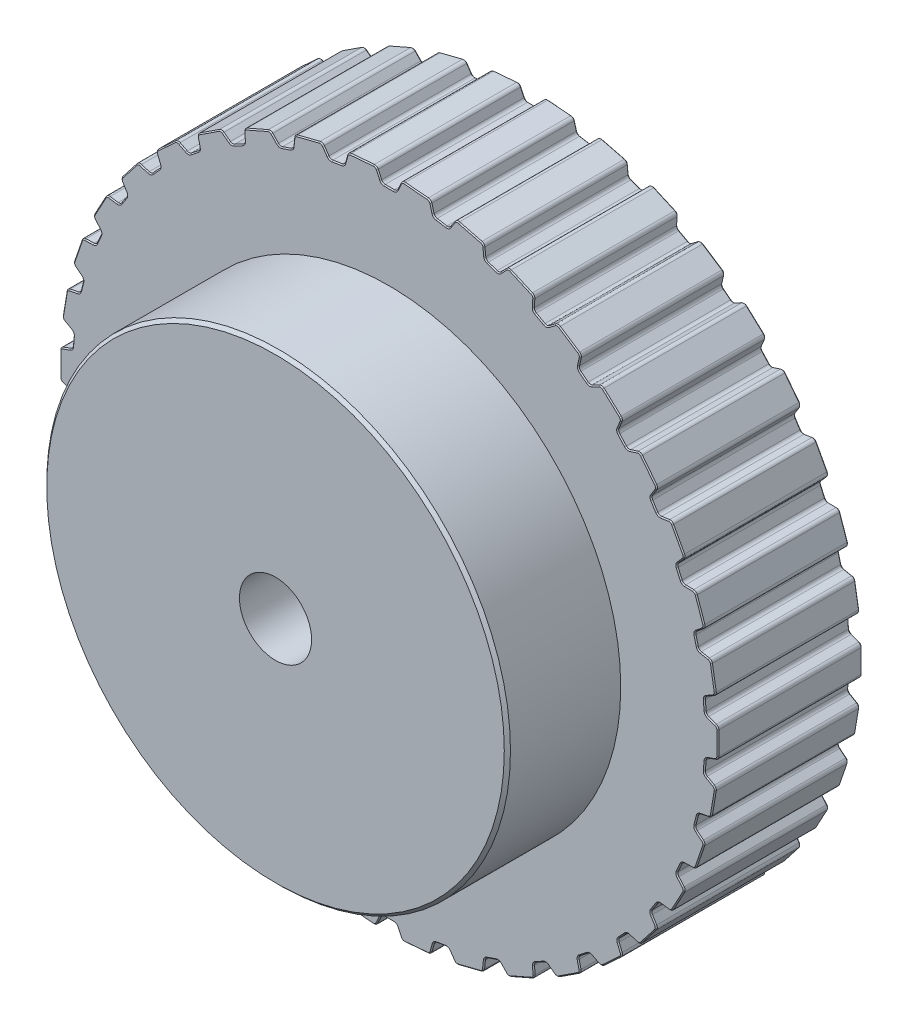
SolidWorks part; units mm, degrees
note: The reader was unsure of these and kept them because the rebuilt part matched: shared geometry of "Sketch2<2>".
ref_plane "Front Plane" through (0, 0, 0) normal (0, 0, 1) x (1, 0, 0)
ref_plane "Top Plane" through (0, 0, 0) normal (0, 1, 0) x (1, 0, 0)
ref_plane "Right Plane" through (0, 0, 0) normal (1, 0, 0) x (0, 0, -1)
sketch "Sketch1" plane through (0, 0, 0) normal (0, 0, 1) x (1, 0, 0)
  circle A0 centre (0, 0) radius 32
  dimension "D1" = 64
extrude "Boss-Extrude1" add sketch "Sketch1" along normal blind 14
sketch "Sketch2" plane through (0, 0, 14) normal (0, 0, 1) x (1, 0, 0)
  circle A0 centre (0, 0) radius 22.5
  circle A1 centre (0, 0) radius 3.5
  dimension "D1" = 45
  dimension "D2" = 7
extrude "Boss-Extrude2" add sketch "Sketch2" along normal blind 11
extrude "Cut-Extrude1" cut sketch "Sketch2<2>" against normal through all contours A1
sketch "Sketch2<2>" plane through (0, 0, 14) normal (0, 0, 1) x (1, 0, 0) same geometry as "Sketch2"
sketch "Sketch3" plane through (0, 0, 14) normal (0, 0, 1) x (1, 0, 0)
  line L0 (0, 0) -> (0, 32) construction
  line L1 (0, 0) -> (5.2718, 31.5628) construction
  line L2 (0.4507, 30.73) -> (-0.4507, 30.73)
  line L3 (-0.7951, 30.9494) -> (-1.1272, 31.6616)
  line L5 (3.7416, 31.694) -> (1.503, 31.8797)
  line L6 (0.7951, 30.9494) -> (1.1272, 31.6616)
  line L7 (6.7617, 31.1896) -> (8.9391, 30.6377)
  line L8 (5.5358, 30.2311) -> (4.5894, 30.3891)
  line L9 (4.2859, 30.6623) -> (4.0763, 31.417)
  line L10 (9.3065, 29.5278) -> (9.2236, 30.3093)
  line L11 (10.4135, 28.9158) -> (9.561, 29.2085)
  line L12 (5.9117, 30.3907) -> (6.3551, 31.0364)
  line L13 (10.8105, 29.0115) -> (11.3559, 29.5773)
  line L14 (13.8391, 28.7591) -> (11.7821, 29.6615)
  line L15 (14.0189, 27.6065) -> (14.0658, 28.3883)
  line L16 (15.0611, 26.7928) -> (14.2173, 27.2496)
  line L17 (15.4685, 26.8218) -> (16.0975, 27.2884)
  line L18 (16.5318, 27.3013) -> (18.412, 26.0723)
  line L19 (18.3992, 24.9033) -> (18.5745, 25.6693)
  line L20 (19.2475, 23.965) -> (18.5362, 24.5186)
  line L21 (19.6541, 23.9266) -> (20.3536, 24.2846)
  line L22 (22.4366, 22.7044) -> (20.7841, 24.2259)
  line L23 (22.2324, 21.5559) -> (22.5306, 22.2802)
  line L24 (22.9539, 20.4479) -> (22.3042, 21.154)
  line L25 (23.3486, 20.3431) -> (24.0951, 20.5802)
  line L26 (24.5101, 20.4514) -> (25.8893, 18.6784)
  line L27 (25.4976, 17.577) -> (25.9122, 18.2445)
  line L28 (25.9953, 16.414) -> (25.5023, 17.1686)
  line L29 (26.3673, 16.2457) -> (27.1452, 16.3572)
  line L30 (28.6023, 14.1863) -> (27.5333, 16.1619)
  line L31 (28.0362, 13.1663) -> (28.5535, 13.7545)
  line L32 (28.3589, 11.884) -> (27.9736, 12.7628)
  line L33 (28.6981, 11.6567) -> (29.4812, 11.6386)
  line L34 (29.8318, 11.382) -> (30.5607, 9.2573)
  line L35 (29.8325, 8.3427) -> (30.4414, 8.8395)
  line L36 (29.9257, 7.0812) -> (29.7044, 7.955)
  line L37 (30.2229, 6.8012) -> (30.9948, 6.6541)
  line L38 (31.6681, 4.1277) -> (31.2985, 6.3433)
  line L39 (30.8015, 3.3468) -> (31.4817, 3.7352)
  line L40 (30.6903, 2.0292) -> (30.6112, 2.9855)
  line L41 (30.9374, 1.7041) -> (31.6721, 1.4327)
  line L42 (31.9205, 1.0761) -> (31.92, -1.1701)
  line L43 (30.9343, -1.7987) -> (31.6714, -1.5266)
  line L44 (30.6127, -3.0221) -> (30.6872, -2.1238)
  line L45 (30.8029, -3.3835) -> (31.4853, -3.7733)
  line L46 (31.3017, -6.3814) -> (31.6716, -4.1658)
  line L47 (30.2286, -6.8386) -> (30.998, -6.6921)
  line L48 (29.6956, -8.0487) -> (29.9313, -7.1186)
  line L49 (29.8237, -8.4364) -> (30.4305, -8.9317)
  line L50 (30.5496, -9.3496) -> (29.8197, -11.4739)
  line L51 (28.6834, -11.7484) -> (29.469, -11.7304)
  line L52 (27.982, -12.8012) -> (28.3441, -11.9757)
  line L53 (28.0446, -13.2047) -> (28.5634, -13.7949)
  line L54 (27.5429, -16.2021) -> (28.6122, -14.2267)
  line L55 (26.3794, -16.2861) -> (27.1548, -16.3974)
  line L56 (25.4824, -17.2576) -> (26.0074, -16.4544)
  line L57 (25.4777, -17.6659) -> (25.8908, -18.3313)
  line L58 (25.8678, -18.7652) -> (24.4877, -20.5375)
  line L59 (23.3238, -20.4281) -> (24.0727, -20.6662)
  line L60 (22.3186, -21.1961) -> (22.9291, -20.5329)
  line L61 (22.2468, -21.5981) -> (22.5458, -22.3248)
  line L62 (20.799, -24.2702) -> (22.4517, -22.749)
  line L63 (19.6713, -23.9719) -> (20.3685, -24.3288)
  line L64 (18.5075, -24.5994) -> (19.2647, -24.0102)
  line L65 (18.3704, -24.9841) -> (18.5451, -25.7476)
  line L66 (18.3824, -26.1505) -> (16.5016, -27.3787)
  line L67 (15.4363, -26.8973) -> (16.0673, -27.3656)
  line L68 (14.2362, -27.2973) -> (15.029, -26.8683)
  line L69 (14.0377, -27.6542) -> (14.0846, -28.4386)
  line L70 (11.8008, -29.7114) -> (13.8579, -28.8093)
  line L71 (10.831, -29.0631) -> (11.3745, -29.6271)
  line L72 (9.5265, -29.2787) -> (10.4341, -28.9673)
  line L73 (9.272, -29.5981) -> (9.1892, -30.3769)
  line L74 (8.9046, -30.7052) -> (6.7269, -31.2561)
  line L75 (5.8756, -30.4549) -> (6.3204, -31.1027)
  line L76 (4.6107, -30.4435) -> (5.4998, -30.2952)
  line L77 (4.3071, -30.7166) -> (4.0967, -31.4738)
  line L78 (1.5234, -31.9361) -> (3.762, -31.7508)
  line L79 (0.8167, -31.008) -> (1.1476, -31.7179)
  line L80 (-0.4872, -30.7884) -> (0.4723, -30.7886)
  line L81 (-0.8316, -31.0078) -> (-1.1628, -31.7176)
  line L82 (-1.5386, -31.9356) -> (-3.7772, -31.7496)
  line L83 (-4.3222, -30.7154) -> (-4.1119, -31.4725)
  line L84 (-5.5149, -30.2939) -> (-4.6258, -30.4423)
  line L85 (-5.8907, -30.4537) -> (-6.3355, -31.1015)
  line L86 (-8.9196, -30.7032) -> (-6.7421, -31.2547)
  line L87 (-9.2866, -29.5959) -> (-9.2041, -30.3748)
  line L88 (-10.4485, -28.9648) -> (-9.5411, -29.2765)
  line L89 (-10.8455, -29.0605) -> (-11.3892, -29.6243)
  line L90 (-11.8155, -29.7085) -> (-13.8723, -28.8057)
  line L91 (-14.052, -27.6505) -> (-14.0989, -28.435)
  line L92 (-15.0433, -26.8646) -> (-14.2505, -27.2937)
  line L93 (-15.4506, -26.8937) -> (-16.0816, -27.362)
  line L94 (-18.3963, -26.1462) -> (-16.5159, -27.3749)
  line L95 (-18.384, -24.9798) -> (-18.5589, -25.7432)
  line L96 (-19.278, -24.0056) -> (-18.5209, -24.5951)
  line L97 (-19.6846, -23.9671) -> (-20.3818, -24.3239)
  line L98 (-20.8124, -24.2651) -> (-22.4646, -22.7434)
  line L99 (-22.2595, -21.5925) -> (-22.5586, -22.3192)
  line L100 (-22.9419, -20.5273) -> (-22.3314, -21.1905)
  line L101 (-23.3365, -20.4225) -> (-24.0854, -20.6606)
  line L102 (-25.88, -18.7591) -> (-24.5004, -20.5318)
  line L103 (-25.4895, -17.6598) -> (-25.9029, -18.3252)
  line L104 (-26.0188, -16.4482) -> (-25.4942, -17.2515)
  line L105 (-26.3909, -16.2798) -> (-27.1662, -16.3908)
  line L106 (-27.5543, -16.1954) -> (-28.623, -14.2197)
  line L107 (-28.0553, -13.1977) -> (-28.5741, -13.7879)
  line L108 (-28.3548, -11.9687) -> (-27.9927, -12.7942)
  line L109 (-28.694, -11.7414) -> (-29.4796, -11.7234)
  line L110 (-30.5595, -9.3423) -> (-29.8303, -11.4669)
  line L111 (-29.8333, -8.4294) -> (-30.4403, -8.9244)
  line L112 (-29.9405, -7.1115) -> (-29.7051, -8.0417)
  line L113 (-30.2377, -6.8314) -> (-31.0071, -6.6847)
  line L114 (-31.3108, -6.3739) -> (-31.68, -4.1582)
  line L115 (-30.8112, -3.3759) -> (-31.4935, -3.7657)
  line L116 (-30.6954, -2.1162) -> (-30.621, -3.0146)
  line L117 (-30.9425, -1.7911) -> (-31.6797, -1.519)
  line L118 (-31.9279, 1.0838) -> (-31.9281, -1.1625)
  line L119 (-30.9446, 1.7114) -> (-31.6795, 1.4403)
  line L120 (-30.6181, 2.9927) -> (-30.6975, 2.0365)
  line L121 (-30.8083, 3.3541) -> (-31.4883, 3.7427)
  line L122 (-31.6746, 4.1353) -> (-31.3044, 6.3508)
  line L123 (-30.2287, 6.8086) -> (-31.0006, 6.6615)
  line L124 (-29.7101, 7.9624) -> (-29.9314, 7.0886)
  line L125 (-29.8383, 8.3501) -> (-30.4472, 8.8469)
  line L126 (-29.8368, 11.3892) -> (-30.5663, 9.2647)
  line L127 (-28.703, 11.6636) -> (-29.4861, 11.6457)
  line L128 (-27.9781, 12.7694) -> (-28.3637, 11.8908)
  line L129 (-28.0407, 13.173) -> (-28.5577, 13.7613)
  line L130 (-28.6064, 14.1931) -> (-27.5369, 16.1684)
  line L131 (-26.3708, 16.2521) -> (-27.1487, 16.3636)
  line L132 (-25.5057, 17.175) -> (-25.9987, 16.4204)
  line L133 (-25.501, 17.5833) -> (-25.9156, 18.2509)
  line L134 (-24.5128, 20.4573) -> (-25.8927, 18.6848)
  line L135 (-23.3514, 20.3487) -> (-24.0978, 20.586)
  line L136 (-22.3067, 21.1592) -> (-22.9567, 20.4534)
  line L137 (-22.2348, 21.5612) -> (-22.5328, 22.2856)
  line L138 (-22.4387, 22.7098) -> (-20.7857, 24.2307)
  line L139 (-19.6557, 23.9313) -> (-20.3552, 24.2893)
  line L140 (-18.5378, 24.5233) -> (-19.2491, 23.9697)
  line L141 (-18.4008, 24.908) -> (-18.5761, 25.674)
  line L142 (-16.5329, 27.3054) -> (-18.4135, 26.0769)
  line L143 (-15.4697, 26.8255) -> (-16.0986, 27.2923)
  line L144 (-14.2185, 27.2529) -> (-15.0624, 26.7964)
  line L145 (-14.0199, 27.6098) -> (-14.0666, 28.3916)
  line L146 (-13.8398, 28.7623) -> (-11.7825, 29.6641)
  line L147 (-10.8109, 29.014) -> (-11.3563, 29.5797)
  line L148 (-9.5614, 29.211) -> (-10.414, 28.9183)
  line L149 (-9.3069, 29.5303) -> (-9.224, 30.3117)
  line L150 (-6.7619, 31.1913) -> (-8.9394, 30.6401)
  line L151 (-5.9121, 30.3922) -> (-6.3553, 31.038)
  line L152 (-4.5898, 30.3902) -> (-5.5363, 30.2324)
  line L153 (-4.2862, 30.6633) -> (-4.0764, 31.4179)
  line L154 (-3.7416, 31.6948) -> (-1.5029, 31.8798)
  circle A0 centre (0, 0) radius 32 construction
  circle A1 centre (0, 0) radius 30.73 construction
  arc A2 (1.503, 31.8797) -> (1.1272, 31.6616) centre (1.4716, 31.501) ccw
  arc A3 (0.4507, 30.73) -> (0.7951, 30.9494) centre (0.4507, 31.11) ccw
  arc A4 (-0.4507, 30.73) -> (-0.7951, 30.9494) centre (-0.4507, 31.11) cw
  arc A5 (8.9391, 30.6377) -> (9.2236, 30.3093) centre (8.8457, 30.2693) cw
  arc A6 (9.561, 29.2085) -> (9.3065, 29.5278) centre (9.6844, 29.5679) cw
  arc A7 (5.5358, 30.2311) -> (5.9117, 30.3907) centre (5.5984, 30.6059) ccw
  arc A8 (4.5894, 30.3891) -> (4.2859, 30.6623) centre (4.652, 30.764) cw
  arc A9 (4.0763, 31.417) -> (3.7416, 31.694) centre (3.7102, 31.3153) ccw
  arc A12 (6.3551, 31.0364) -> (6.7617, 31.1896) centre (6.6683, 30.8212) cw
  arc A13 (10.4135, 28.9158) -> (10.8105, 29.0115) centre (10.5369, 29.2752) ccw
  arc A14 (11.7821, 29.6615) -> (11.3559, 29.5773) centre (11.6295, 29.3136) ccw
  arc A15 (14.0658, 28.3883) -> (13.8391, 28.7591) centre (13.6865, 28.4111) ccw
  arc A16 (14.2173, 27.2496) -> (14.0189, 27.6065) centre (14.3982, 27.5838) cw
  arc A17 (15.0611, 26.7928) -> (15.4685, 26.8218) centre (15.2421, 27.1269) ccw
  arc A18 (16.0975, 27.2884) -> (16.5318, 27.3013) centre (16.3239, 26.9832) cw
  arc A19 (18.412, 26.0723) -> (18.5745, 25.6693) centre (18.2041, 25.7542) cw
  arc A20 (18.5362, 24.5186) -> (18.3992, 24.9033) centre (18.7696, 24.8185) cw
  arc A21 (19.2475, 23.965) -> (19.6541, 23.9266) centre (19.4809, 24.2649) ccw
  arc A22 (20.7841, 24.2259) -> (20.3536, 24.2846) centre (20.5267, 23.9464) ccw
  arc A23 (22.5306, 22.2802) -> (22.4366, 22.7044) centre (22.1792, 22.4249) ccw
  arc A24 (22.3042, 21.154) -> (22.2324, 21.5559) centre (22.5838, 21.4113) cw
  arc A25 (22.9539, 20.4479) -> (23.3486, 20.3431) centre (23.2336, 20.7052) ccw
  arc A26 (24.0951, 20.5802) -> (24.5101, 20.4514) centre (24.2101, 20.218) cw
  arc A27 (25.8893, 18.6784) -> (25.9122, 18.2445) centre (25.5894, 18.4451) cw
  arc A28 (25.5023, 17.1686) -> (25.4976, 17.577) centre (25.8204, 17.3765) cw
  arc A29 (25.9953, 16.414) -> (26.3673, 16.2457) centre (26.3134, 16.6219) ccw
  arc A30 (27.5333, 16.1619) -> (27.1452, 16.3572) centre (27.1991, 15.9811) ccw
  arc A31 (28.5535, 13.7545) -> (28.6023, 14.1863) centre (28.2681, 14.0055) ccw
  arc A32 (27.9736, 12.7628) -> (28.0362, 13.1663) centre (28.3216, 12.9154) cw
  arc A33 (28.3589, 11.884) -> (28.6981, 11.6567) centre (28.7069, 12.0366) ccw
  arc A34 (29.4812, 11.6386) -> (29.8318, 11.382) centre (29.4724, 11.2587) cw
  arc A35 (30.5607, 9.2573) -> (30.4414, 8.8395) centre (30.2013, 9.134) cw
  arc A36 (29.7044, 7.955) -> (29.8325, 8.3427) centre (30.0728, 8.0483) cw
  arc A37 (29.9257, 7.0812) -> (30.2229, 6.8012) centre (30.294, 7.1745) ccw
  arc A38 (31.2985, 6.3433) -> (30.9948, 6.6541) centre (30.9237, 6.2808) ccw
  arc A39 (31.4817, 3.7352) -> (31.6681, 4.1277) centre (31.2933, 4.0652) ccw
  arc A40 (30.6112, 2.9855) -> (30.8015, 3.3468) centre (30.99, 3.0168) cw
  arc A41 (30.6903, 2.0292) -> (30.9374, 1.7041) centre (31.069, 2.0605) ccw
  arc A42 (31.6721, 1.4327) -> (31.9205, 1.0761) centre (31.5405, 1.0762) cw
  arc A43 (31.92, -1.1701) -> (31.6714, -1.5266) centre (31.54, -1.17) cw
  arc A44 (30.6872, -2.1238) -> (30.9343, -1.7987) centre (31.0659, -2.1552) cw
  arc A45 (30.6127, -3.0221) -> (30.8029, -3.3835) centre (30.9914, -3.0535) ccw
  arc A46 (31.6716, -4.1658) -> (31.4853, -3.7733) centre (31.2968, -4.1032) ccw
  arc A47 (30.998, -6.6921) -> (31.3017, -6.3814) centre (30.9269, -6.3188) ccw
  arc A48 (29.9313, -7.1186) -> (30.2286, -6.8386) centre (30.2996, -7.2119) cw
  arc A49 (29.6956, -8.0487) -> (29.8237, -8.4364) centre (30.0639, -8.142) ccw
  arc A50 (30.4305, -8.9317) -> (30.5496, -9.3496) centre (30.1902, -9.2261) cw
  arc A51 (29.8197, -11.4739) -> (29.469, -11.7304) centre (29.4604, -11.3505) cw
  arc A52 (28.3441, -11.9757) -> (28.6834, -11.7484) centre (28.6921, -12.1283) cw
  arc A53 (27.982, -12.8012) -> (28.0446, -13.2047) centre (28.33, -12.9538) ccw
  arc A54 (28.6122, -14.2267) -> (28.5634, -13.7949) centre (28.278, -14.0458) ccw
  arc A55 (27.1548, -16.3974) -> (27.5429, -16.2021) centre (27.2087, -16.0212) ccw
  arc A56 (26.0074, -16.4544) -> (26.3794, -16.2861) centre (26.3255, -16.6622) cw
  arc A57 (25.4824, -17.2576) -> (25.4777, -17.6659) centre (25.8005, -17.4654) ccw
  arc A58 (25.8908, -18.3313) -> (25.8678, -18.7652) centre (25.568, -18.5318) cw
  arc A59 (24.4877, -20.5375) -> (24.0727, -20.6662) centre (24.1879, -20.304) cw
  arc A60 (22.9291, -20.5329) -> (23.3238, -20.4281) centre (23.2087, -20.7903) cw
  arc A61 (22.3186, -21.1961) -> (22.2468, -21.5981) centre (22.5982, -21.4535) ccw
  arc A62 (22.4517, -22.749) -> (22.5458, -22.3248) centre (22.1944, -22.4694) ccw
  arc A63 (20.3685, -24.3288) -> (20.799, -24.2702) centre (20.5417, -23.9906) ccw
  arc A64 (19.2647, -24.0102) -> (19.6713, -23.9719) centre (19.4981, -24.3101) cw
  arc A65 (18.5075, -24.5994) -> (18.3704, -24.9841) centre (18.7408, -24.8993) ccw
  arc A66 (18.5451, -25.7476) -> (18.3824, -26.1505) centre (18.1746, -25.8324) cw
  arc A67 (16.5016, -27.3787) -> (16.0673, -27.3656) centre (16.2939, -27.0605) cw
  arc A68 (15.029, -26.8683) -> (15.4363, -26.8973) centre (15.2098, -27.2025) cw
  arc A69 (14.2362, -27.2973) -> (14.0377, -27.6542) centre (14.4171, -27.6315) ccw
  arc A70 (13.8579, -28.8093) -> (14.0846, -28.4386) centre (13.7053, -28.4613) ccw
  arc A71 (11.3745, -29.6271) -> (11.8008, -29.7114) centre (11.6482, -29.3634) ccw
  arc A72 (10.4341, -28.9673) -> (10.831, -29.0631) centre (10.5574, -29.3268) cw
  arc A73 (9.5265, -29.2787) -> (9.272, -29.5981) centre (9.6498, -29.6382) ccw
  arc A74 (9.1892, -30.3769) -> (8.9046, -30.7052) centre (8.8114, -30.3368) cw
  arc A75 (6.7269, -31.2561) -> (6.3204, -31.1027) centre (6.6337, -30.8877) cw
  arc A76 (5.4998, -30.2952) -> (5.8756, -30.4549) centre (5.5623, -30.67) cw
  arc A77 (4.6107, -30.4435) -> (4.3071, -30.7166) centre (4.6732, -30.8184) ccw
  arc A78 (3.762, -31.7508) -> (4.0967, -31.4738) centre (3.7306, -31.3721) ccw
  arc A79 (1.1476, -31.7179) -> (1.5234, -31.9361) centre (1.492, -31.5574) ccw
  arc A80 (0.4723, -30.7886) -> (0.8167, -31.008) centre (0.4723, -31.1686) cw
  arc A81 (-0.4872, -30.7884) -> (-0.8316, -31.0078) centre (-0.4873, -31.1684) ccw
  arc A82 (-1.1628, -31.7176) -> (-1.5386, -31.9356) centre (-1.5071, -31.5569) cw
  arc A83 (-3.7772, -31.7496) -> (-4.1119, -31.4725) centre (-3.7457, -31.3709) cw
  arc A84 (-4.6258, -30.4423) -> (-4.3222, -30.7154) centre (-4.6883, -30.8171) cw
  arc A85 (-5.5149, -30.2939) -> (-5.8907, -30.4537) centre (-5.5774, -30.6687) ccw
  arc A86 (-6.7421, -31.2547) -> (-6.3355, -31.1015) centre (-6.6488, -30.8864) ccw
  arc A87 (-9.2041, -30.3748) -> (-8.9196, -30.7032) centre (-8.8263, -30.3348) ccw
  arc A88 (-9.5411, -29.2765) -> (-9.2866, -29.5959) centre (-9.6645, -29.6359) cw
  arc A89 (-10.4485, -28.9648) -> (-10.8455, -29.0605) centre (-10.572, -29.3242) ccw
  arc A90 (-11.3892, -29.6243) -> (-11.8155, -29.7085) centre (-11.6628, -29.3605) cw
  arc A91 (-13.8723, -28.8057) -> (-14.0989, -28.435) centre (-13.7196, -28.4578) cw
  arc A92 (-14.2505, -27.2937) -> (-14.052, -27.6505) centre (-14.4314, -27.6279) cw
  arc A93 (-15.0433, -26.8646) -> (-15.4506, -26.8937) centre (-15.2241, -27.1988) ccw
  arc A94 (-16.5159, -27.3749) -> (-16.0816, -27.362) centre (-16.3081, -27.0568) ccw
  arc A95 (-18.5589, -25.7432) -> (-18.3963, -26.1462) centre (-18.1885, -25.8281) ccw
  arc A96 (-18.5209, -24.5951) -> (-18.384, -24.9798) centre (-18.7544, -24.8949) cw
  arc A97 (-19.278, -24.0056) -> (-19.6846, -23.9671) centre (-19.5115, -24.3054) ccw
  arc A98 (-20.3818, -24.3239) -> (-20.8124, -24.2651) centre (-20.5549, -23.9856) cw
  arc A99 (-22.4646, -22.7434) -> (-22.5586, -22.3192) centre (-22.2072, -22.4639) cw
  arc A100 (-22.3314, -21.1905) -> (-22.2595, -21.5925) centre (-22.6109, -21.4479) cw
  arc A101 (-22.9419, -20.5273) -> (-23.3365, -20.4225) centre (-23.2214, -20.7847) ccw
  arc A102 (-24.5004, -20.5318) -> (-24.0854, -20.6606) centre (-24.2005, -20.2984) ccw
  arc A103 (-25.9029, -18.3252) -> (-25.88, -18.7591) centre (-25.5801, -18.5257) ccw
  arc A104 (-25.4942, -17.2515) -> (-25.4895, -17.6598) centre (-25.8123, -17.4593) cw
  arc A105 (-26.0188, -16.4482) -> (-26.3909, -16.2798) centre (-26.337, -16.656) ccw
  arc A106 (-27.1662, -16.3908) -> (-27.5543, -16.1954) centre (-27.2201, -16.0147) cw
  arc A107 (-28.623, -14.2197) -> (-28.5741, -13.7879) centre (-28.2887, -14.0389) cw
  arc A108 (-27.9927, -12.7942) -> (-28.0553, -13.1977) centre (-28.3407, -12.9468) cw
  arc A109 (-28.3548, -11.9687) -> (-28.694, -11.7414) centre (-28.7028, -12.1213) ccw
  arc A110 (-29.8303, -11.4669) -> (-29.4796, -11.7234) centre (-29.4709, -11.3435) ccw
  arc A111 (-30.4403, -8.9244) -> (-30.5595, -9.3423) centre (-30.2001, -9.2189) ccw
  arc A112 (-29.7051, -8.0417) -> (-29.8333, -8.4294) centre (-30.0735, -8.1349) cw
  arc A113 (-29.9405, -7.1115) -> (-30.2377, -6.8314) centre (-30.3089, -7.2047) ccw
  arc A114 (-31.0071, -6.6847) -> (-31.3108, -6.3739) centre (-30.9359, -6.3114) cw
  arc A115 (-31.68, -4.1582) -> (-31.4935, -3.7657) centre (-31.3051, -4.0957) cw
  arc A116 (-30.621, -3.0146) -> (-30.8112, -3.3759) centre (-30.9997, -3.0459) cw
  arc A117 (-30.6954, -2.1162) -> (-30.9425, -1.7911) centre (-31.0741, -2.1476) ccw
  arc A118 (-31.9281, -1.1625) -> (-31.6797, -1.519) centre (-31.5481, -1.1625) ccw
  arc A119 (-31.6795, 1.4403) -> (-31.9279, 1.0838) centre (-31.5479, 1.0838) ccw
  arc A120 (-30.6975, 2.0365) -> (-30.9446, 1.7114) centre (-31.0762, 2.0679) cw
  arc A121 (-30.6181, 2.9927) -> (-30.8083, 3.3541) centre (-30.9968, 3.0242) ccw
  arc A122 (-31.4883, 3.7427) -> (-31.6746, 4.1353) centre (-31.2998, 4.0726) cw
  arc A123 (-31.3044, 6.3508) -> (-31.0006, 6.6615) centre (-30.9296, 6.2882) cw
  arc A124 (-29.9314, 7.0886) -> (-30.2287, 6.8086) centre (-30.2998, 7.1819) cw
  arc A125 (-29.7101, 7.9624) -> (-29.8383, 8.3501) centre (-30.0785, 8.0557) ccw
  arc A126 (-30.5663, 9.2647) -> (-30.4472, 8.8469) centre (-30.2069, 9.1413) ccw
  arc A127 (-29.4861, 11.6457) -> (-29.8368, 11.3892) centre (-29.4774, 11.2658) ccw
  arc A128 (-28.3637, 11.8908) -> (-28.703, 11.6636) centre (-28.7117, 12.0435) cw
  arc A129 (-27.9781, 12.7694) -> (-28.0407, 13.173) centre (-28.3261, 12.9221) ccw
  arc A130 (-28.5577, 13.7613) -> (-28.6064, 14.1931) centre (-28.2722, 14.0122) cw
  arc A131 (-27.5369, 16.1684) -> (-27.1487, 16.3636) centre (-27.2027, 15.9875) cw
  arc A132 (-25.9987, 16.4204) -> (-26.3708, 16.2521) centre (-26.3169, 16.6282) cw
  arc A133 (-25.5057, 17.175) -> (-25.501, 17.5833) centre (-25.8238, 17.3829) ccw
  arc A134 (-25.8927, 18.6848) -> (-25.9156, 18.2509) centre (-25.5928, 18.4514) ccw
  arc A135 (-24.0978, 20.586) -> (-24.5128, 20.4573) centre (-24.213, 20.2239) ccw
  arc A136 (-22.9567, 20.4534) -> (-23.3514, 20.3487) centre (-23.2363, 20.7108) cw
  arc A137 (-22.3067, 21.1592) -> (-22.2348, 21.5612) centre (-22.5863, 21.4166) ccw
  arc A138 (-22.5328, 22.2856) -> (-22.4387, 22.7098) centre (-22.1814, 22.4301) cw
  arc A139 (-20.7857, 24.2307) -> (-20.3552, 24.2893) centre (-20.5284, 23.9511) cw
  arc A140 (-19.2491, 23.9697) -> (-19.6557, 23.9313) centre (-19.4825, 24.2695) cw
  arc A141 (-18.5378, 24.5233) -> (-18.4008, 24.908) centre (-18.7712, 24.8232) ccw
  arc A142 (-18.4135, 26.0769) -> (-18.5761, 25.674) centre (-18.2057, 25.7588) ccw
  arc A143 (-16.0986, 27.2923) -> (-16.5329, 27.3054) centre (-16.3251, 26.9872) ccw
  arc A144 (-15.0624, 26.7964) -> (-15.4697, 26.8255) centre (-15.2432, 27.1306) cw
  arc A145 (-14.2185, 27.2529) -> (-14.0199, 27.6098) centre (-14.3993, 27.5872) ccw
  arc A146 (-14.0666, 28.3916) -> (-13.8398, 28.7623) centre (-13.6872, 28.4143) cw
  arc A147 (-11.7825, 29.6641) -> (-11.3563, 29.5797) centre (-11.63, 29.3161) cw
  arc A148 (-10.414, 28.9183) -> (-10.8109, 29.014) centre (-10.5373, 29.2777) cw
  arc A149 (-9.5614, 29.211) -> (-9.3069, 29.5303) centre (-9.6848, 29.5704) ccw
  arc A150 (-8.9394, 30.6401) -> (-9.224, 30.3117) centre (-8.8462, 30.2717) ccw
  arc A151 (-6.3553, 31.038) -> (-6.7619, 31.1913) centre (-6.6686, 30.8229) ccw
  arc A152 (-5.5363, 30.2324) -> (-5.9121, 30.3922) centre (-5.5988, 30.6072) cw
  arc A153 (-4.5898, 30.3902) -> (-4.2862, 30.6633) centre (-4.6523, 30.765) ccw
  arc A154 (-4.0764, 31.4179) -> (-3.7416, 31.6948) centre (-3.7103, 31.3161) cw
  arc A155 (-1.5029, 31.8798) -> (-1.1272, 31.6616) centre (-1.4716, 31.5011) cw
  point P9 (0, 30.73)
  point P11 (0, 0)
  point P12 (0, 0)
  point P21 (0.6928, 30.73)
  point P24 (-0.6928, 30.73)
  point P34 (5.0626, 30.3101)
  point P35 (5.7746, 30.1912)
  point P38 (4.3506, 30.429)
  point P495 (-0.0038, -0.0291)
  dimension "D1" = 64
  dimension "D2" = 1.27
  dimension "D5" = 1.27
  dimension "D11" = 0.38
  dimension "D13" = 1.5902
  dimension "D3" = 50
  dimension "D4" = 19
  dimension "D6" = 5.08
  dimension "D8" = 50
  dimension "D10" = 1.27
  dimension "D12" = 1.6483
extrude "Cut-Extrude2" cut sketch "Sketch3" against normal through all flip side to cut
chamfer "Chamfer1" distance 0.1 angle 45 400 edges at (0.9611, 31.3055, 0) (0.6549, 30.7895, 0) (0, 30.73, 0) (-0.6549, 30.7895, 0) (-0.9611, 31.3055, 0) (-1.2808, 31.8297, 0) (-2.6223, 31.7873, 0) (-3.9525, 31.6089, 0) (-4.1813, 31.0406, 0) (-4.3982, 30.4825, 0) (-5.063, 30.3113, 0) (-5.7474, 30.2575, 0) (-6.1337, 30.7151, 0) (-6.5345, 31.1785, 0) (-7.8506, 30.9157, 0) (-9.1333, 30.5206, 0) (-9.2655, 29.921, 0) (-9.3876, 29.3335, 0) (-9.9877, 29.0646, 0) (-10.6264, 28.9083, 0) (-11.0836, 29.2969, 0) (-11.5562, 29.6889, 0) (-12.8112, 29.2132, 0) (-14.0114, 28.6126, 0) (-14.0432, 28.0007, 0) (-14.0672, 27.4024, 0) (-14.6404, 27.0247, 0) (-15.2703, 26.7516, 0) (-15.7842, 27.0589, 0) (-16.3137, 27.3671, 0) (-17.4732, 26.6911, 0) (-18.5581, 25.901, 0) (-18.4884, 25.291, 0) (-18.4132, 24.6957, 0) (-18.8934, 24.2465, 0) (-19.4468, 23.8912, 0) (-20.0054, 24.1103, 0) (-20.5796, 24.3276, 0) (-21.6122, 23.4702, 0) (-22.5524, 22.5124, 0) (-22.3838, 21.9234, 0) (-22.2122, 21.3497, 0) (-22.6317, 20.8063, 0) (-23.1388, 20.3435, 0) (-23.7246, 20.4673, 0) (-24.3255, 20.5868, 0) (-25.2028, 19.5711, 0) (-25.9723, 18.4715, 0) (-25.7083, 17.9171, 0) (-25.4439, 17.3785, 0) (-25.7522, 16.7977, 0) (-26.1602, 16.282, 0) (-26.7597, 16.3078, 0) (-27.3734, 16.3269, 0) (-28.0716, 15.1807, 0) (-28.6498, 13.9696, 0) (-28.2992, 13.4672, 0) (-27.9506, 12.9803, 0) (-28.1709, 12.3301, 0) (-28.5003, 11.7277, 0) (-29.0946, 11.6546, 0) (-29.7017, 11.5725, 0) (-30.2016, 10.327, 0) (-30.5724, 9.0371, 0) (-30.1427, 8.5985, 0) (-29.7177, 8.1749, 0) (-29.8208, 7.5255, 0) (-30.0392, 6.9053, 0) (-30.6146, 6.735, 0) (-31.2013, 6.5538, 0) (-31.4895, 5.243, 0) (-31.6431, 3.9097, 0) (-31.1483, 3.5484, 0) (-30.6605, 3.2011, 0) (-30.6578, 2.5146, 0) (-30.7737, 1.8379, 0) (-31.312, 1.5758, 0) (-31.8597, 1.301, 0) (-31.928, -0.0393, 0) (-31.8599, -1.3797, 0) (-31.3111, -1.6551, 0) (-30.7716, -1.9177, 0) (-30.6582, -2.5654, 0) (-30.6634, -3.223, 0) (-31.1524, -3.5708, 0) (-31.6484, -3.9326, 0) (-31.4954, -5.266, 0) (-31.2077, -6.5769, 0) (-30.6224, -6.758, 0) (-30.0483, -6.9281, 0) (-29.8228, -7.5766, 0) (-29.7127, -8.2542, 0) (-30.1368, -8.6769, 0) (-30.5655, -9.1146, 0) (-30.1949, -10.4046, 0) (-29.6953, -11.6502, 0) (-29.0868, -11.7324, 0) (-28.4913, -11.8056, 0) (-28.1737, -12.3814, 0) (-27.9652, -13.0051, 0) (-28.3147, -13.4928, 0) (-28.6663, -13.9961, 0) (-28.0886, -15.2076, 0) (-27.3909, -16.3541, 0) (-26.7785, -16.3353, 0) (-26.1803, -16.3098, 0) (-25.7565, -16.8498, 0) (-25.4323, -17.455, 0) (-25.6962, -17.9925, 0) (-25.9596, -18.5457, 0) (-25.1902, -19.6454, 0) (-24.3132, -20.6613, 0) (-23.711, -20.5416, 0) (-23.1239, -20.4174, 0) (-22.6366, -20.8589, 0) (-22.2369, -21.381, 0) (-22.409, -21.9558, 0) (-22.5782, -22.546, 0) (-21.6385, -23.5043, 0) (-20.6063, -24.3621, 0) (-20.0332, -24.1455, 0) (-19.4757, -23.9271, 0) (-18.8995, -24.3003, 0) (-18.3964, -24.7675, 0) (-18.4714, -25.3615, 0) (-18.5409, -25.9703, 0) (-17.4561, -26.7606, 0) (-16.2967, -27.4367, 0) (-15.7661, -27.1278, 0) (-15.2511, -26.8198, 0) (-14.6469, -27.0792, 0) (-14.0993, -27.4432, 0) (-14.0755, -28.0428, 0) (-14.0438, -28.6559, 0) (-12.8439, -29.2571, 0) (-11.5891, -29.7333, 0) (-11.1174, -29.3424, 0) (-10.661, -28.9548, 0) (-9.9948, -29.1207, 0) (-9.3673, -29.3991, 0) (-9.2454, -29.9854, 0) (-9.1134, -30.5837, 0) (-7.8308, -30.979, 0) (-6.5147, -31.242, 0) (-6.1131, -30.7776, 0) (-5.7261, -30.319, 0) (-5.0703, -30.3681, 0) (-4.4342, -30.5346, 0) (-4.217, -31.094, 0) (-3.988, -31.6636, 0) (-2.6579, -31.8426, 0) (-1.3165, -31.8856, 0) (-0.9972, -31.3627, 0) (-0.6914, -30.8479, 0) (-0.0075, -30.7885, 0) (0.6765, -30.8481, 0) (0.9821, -31.363, 0) (1.3012, -31.886, 0) (2.6427, -31.8434, 0) (3.9728, -31.6648, 0) (4.2019, -31.0952, 0) (4.4191, -30.5359, 0) (5.0552, -30.3694, 0) (5.711, -30.3203, 0) (6.098, -30.7788, 0) (6.4996, -31.2433, 0) (7.8157, -30.9807, 0) (9.0985, -30.5858, 0) (9.2306, -29.9875, 0) (9.3527, -29.4013, 0) (9.9803, -29.123, 0) (10.6465, -28.9574, 0) (11.1028, -29.3451, 0) (11.5744, -29.7362, 0) (12.8294, -29.2603, 0) (14.0295, -28.6595, 0) (14.0612, -28.0464, 0) (14.085, -27.4468, 0) (14.6326, -27.0828, 0) (15.2368, -26.8234, 0) (15.7518, -27.1315, 0) (16.2824, -27.4404, 0) (17.442, -26.7646, 0) (18.527, -25.9746, 0) (18.4577, -25.3659, 0) (18.3829, -24.7718, 0) (18.8861, -24.3048, 0) (19.4624, -23.9318, 0) (20.0199, -24.1504, 0) (20.5929, -24.3671, 0) (21.6254, -23.5096, 0) (22.5654, -22.5517, 0) (22.3963, -21.9614, 0) (22.2241, -21.3866, 0) (22.6238, -20.8645, 0) (23.1112, -20.423, 0) (23.6982, -20.5471, 0) (24.3004, -20.667, 0) (25.1777, -19.6514, 0) (25.9474, -18.5519, 0) (25.6842, -17.9986, 0) (25.4205, -17.461, 0) (25.7449, -16.856, 0) (26.1689, -16.316, 0) (26.7671, -16.3417, 0) (27.3795, -16.3607, 0) (28.0775, -15.2144, 0) (28.6556, -14.0031, 0) (28.304, -13.4998, 0) (27.9545, -13.012, 0) (28.1631, -12.3884, 0) (28.4806, -11.8126, 0) (29.0762, -11.7394, 0) (29.6846, -11.6572, 0) (30.1847, -10.4117, 0) (30.5557, -9.1219, 0) (30.1271, -8.6841, 0) (29.7031, -8.2612, 0) (29.8134, -7.5836, 0) (30.0391, -6.9353, 0) (30.6133, -6.7654, 0) (31.1986, -6.5844, 0) (31.4867, -5.2736, 0) (31.6401, -3.9403, 0) (31.1441, -3.5784, 0) (30.6552, -3.2305, 0) (30.6499, -2.573, 0) (30.7633, -1.9253, 0) (31.3029, -1.6626, 0) (31.8517, -1.3874, 0) (31.9202, -0.047, 0) (31.8523, 1.2934, 0) (31.3048, 1.5684, 0) (30.7665, 1.8306, 0) (30.6508, 2.5073, 0) (30.6537, 3.1938, 0) (31.1416, 3.541, 0) (31.6365, 3.9022, 0) (31.4833, 5.2355, 0) (31.1955, 6.5464, 0) (30.6089, 6.7276, 0) (30.0335, 6.8979, 0) (29.815, 7.5181, 0) (29.712, 8.1676, 0) (30.137, 8.5911, 0) (30.5667, 9.0297, 0) (30.1963, 10.3197, 0) (29.6968, 11.5654, 0) (29.0897, 11.6477, 0) (28.4954, 11.7209, 0) (28.1663, 12.3234, 0) (27.9461, 12.9737, 0) (28.2949, 13.4604, 0) (28.6457, 13.9627, 0) (28.0678, 15.1741, 0) (27.3699, 16.3205, 0) (26.7563, 16.3015, 0) (26.1568, 16.2756, 0) (25.7488, 16.7913, 0) (25.4404, 17.3721, 0) (25.7049, 17.9107, 0) (25.9689, 18.4651, 0) (25.1997, 19.5649, 0) (24.3228, 20.5809, 0) (23.7218, 20.4616, 0) (23.136, 20.338, 0) (22.6291, 20.8009, 0) (22.2097, 21.3445, 0) (22.3815, 21.9181, 0) (22.5502, 22.5071, 0) (21.6103, 23.4652, 0) (20.578, 24.3229, 0) (20.0038, 24.1056, 0) (19.4452, 23.8865, 0) (18.8918, 24.2418, 0) (18.4116, 24.691, 0) (18.4868, 25.2863, 0) (18.5566, 25.8963, 0) (17.4719, 26.6868, 0) (16.3127, 27.3631, 0) (15.783, 27.0551, 0) (15.269, 26.7479, 0) (14.6392, 27.0212, 0) (14.0661, 27.3991, 0) (14.0424, 27.9974, 0) (14.0107, 28.6093, 0) (12.8106, 29.2103, 0) (11.5558, 29.6863, 0) (11.0832, 29.2944, 0) (10.626, 28.9058, 0) (9.9873, 29.0622, 0) (9.3872, 29.3311, 0) (9.2651, 29.9186, 0) (9.1329, 30.5182, 0) (7.8504, 30.9136, 0) (6.5343, 31.1768, 0) (6.1334, 30.7136, 0) (5.747, 30.2561, 0) (5.0626, 30.3101, 0) (4.3978, 30.4815, 0) (4.1811, 31.0396, 0) (3.9524, 31.6081, 0) (2.6223, 31.7869, 0) (1.2809, 31.8297, 0) (3.5, 0, 0) (21.6254, -23.5096, 14) (22.5654, -22.5517, 14) (20.5929, -24.3671, 14) (22.3963, -21.9614, 14) (20.0199, -24.1504, 14) (22.2241, -21.3866, 14) (19.4624, -23.9318, 14) (22.6238, -20.8645, 14) (18.8861, -24.3048, 14) (23.1112, -20.423, 14) (18.3829, -24.7718, 14) (23.6982, -20.5471, 14) (18.4577, -25.3659, 14) (24.3004, -20.667, 14) (18.527, -25.9746, 14) (25.1777, -19.6514, 14) (17.442, -26.7646, 14) (25.9474, -18.5519, 14) (16.2824, -27.4404, 14) (25.6842, -17.9986, 14) (15.7518, -27.1315, 14) (25.4205, -17.461, 14) (15.2368, -26.8234, 14) (25.7449, -16.856, 14) (14.6326, -27.0828, 14) (26.1689, -16.316, 14) (14.085, -27.4468, 14) (26.7671, -16.3417, 14) (14.0612, -28.0464, 14) (27.3795, -16.3607, 14) (14.0295, -28.6595, 14) (28.0775, -15.2144, 14) (12.8294, -29.2603, 14) (28.6556, -14.0031, 14) (11.5744, -29.7362, 14) (28.304, -13.4998, 14) (11.1028, -29.3451, 14) (27.9545, -13.012, 14) (10.6465, -28.9574, 14) (28.1631, -12.3884, 14) (9.9803, -29.123, 14) (28.4806, -11.8126, 14) (9.3527, -29.4013, 14) (29.0762, -11.7394, 14) (9.2306, -29.9875, 14) (29.6846, -11.6572, 14) (9.0985, -30.5858, 14) (30.1847, -10.4117, 14) (7.8157, -30.9807, 14) (30.5557, -9.1219, 14) (6.4996, -31.2433, 14) (30.1271, -8.6841, 14) (6.098, -30.7788, 14) (29.7031, -8.2612, 14) (5.711, -30.3203, 14) (29.8134, -7.5836, 14) (5.0552, -30.3694, 14) (30.0391, -6.9353, 14) (4.4191, -30.5359, 14) (30.6133, -6.7654, 14) (4.2019, -31.0952, 14) (31.1986, -6.5844, 14) (3.9728, -31.6648, 14) (31.4867, -5.2736, 14) (2.6427, -31.8434, 14) (31.6401, -3.9403, 14) (1.3012, -31.886, 14) (31.1441, -3.5784, 14) (0.9821, -31.363, 14) (30.6552, -3.2305, 14) (0.6765, -30.8481, 14) (30.6499, -2.573, 14) (-0.0075, -30.7885, 14) (30.7633, -1.9253, 14) (-0.6914, -30.8479, 14) (31.3029, -1.6626, 14) (-0.9972, -31.3627, 14) (31.8517, -1.3874, 14) (-1.3165, -31.8856, 14) (31.9202, -0.047, 14) (-2.6579, -31.8426, 14) (31.8523, 1.2934, 14) (-3.988, -31.6636, 14) (31.3048, 1.5684, 14) (-4.217, -31.094, 14) (30.7665, 1.8306, 14) (-4.4342, -30.5346, 14) (30.6508, 2.5073, 14) (-5.0703, -30.3681, 14) (30.6537, 3.1938, 14) (-5.7261, -30.319, 14) (31.1416, 3.541, 14) (-6.1131, -30.7776, 14) (31.6365, 3.9022, 14) (-6.5147, -31.242, 14)
chamfer "Chamfer2" distance 0.3 angle 45 1 edges at (22.5, 0, 25)
